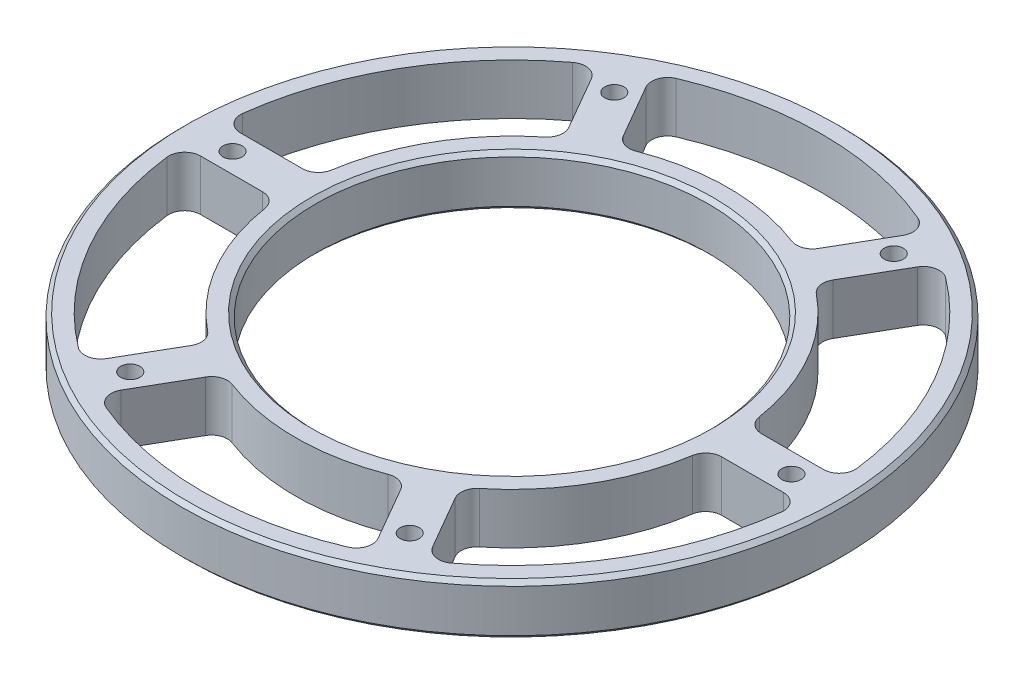
SolidWorks part; units mm, degrees
material "6061-T6 (SS)"
ref_plane "Front Plane" through (0, 0, 0) normal (0, 0, 1) x (1, 0, 0)
ref_plane "Top Plane" through (0, 0, 0) normal (0, 1, 0) x (1, 0, 0)
ref_plane "Right Plane" through (0, 0, 0) normal (1, 0, 0) x (0, 0, -1)
sketch "Sketch2" plane through (0, 0, 0) normal (1, 0, 0) x (0, 0, -1)
  line L0 (-49.2125, 0) -> (-82.55, 0)
  line L1 (-82.55, 0) -> (-82.55, 12.7)
  line L2 (-82.55, 12.7) -> (-49.2125, 12.7)
  line L3 (-49.2125, 12.7) -> (-49.2125, 0)
  dimension "D1" = 82.55
  dimension "D2" = 12.7
  dimension "D4" = 49.2125
ref_axis "Axis1" through (0, -0.635, 0) along (0, 1, 0)
revolve "Revolve1" add sketch "Sketch2" angle 360 about axis through (0, -0.635, 0) along (0, 1, 0)
hole_wizard "#12 (0.189) Diameter Hole1" positions "Sketch6" profile "Sketch7" hole size "#12" standard "ANSI Inch" end condition through all
sketch "Sketch6" plane through (0, 12.7, 0) normal (0, 1, 0) x (1, 0, 0)
  line L0 (0, 0) -> (-69.8201, 120.932) construction
  line L2 (0, 0) -> (0, 109.0908) construction
  point P0 (-35, 60.6218)
  dimension "D1" = 30
  dimension "D2" = 70
sketch "Sketch7" plane through (-35, 12.7, -60.6218) normal (1, 0, 0) x (0, 0, 1)
  line L0 (0, 0) -> (0, 12.7)
  line L1 (0, 12.7) -> (2.4003, 12.7)
  line L2 (2.4003, 12.7) -> (2.4003, 0)
  line L5 (2.4003, 0) -> (0, 0)
  line L11 (0, -6.35) -> (0, 107.95) construction
  dimension "Thru Hole Dia." = 4.8006
  dimension "Thru Hole Depth" = 12.7
pattern_circular "CirPattern3" count 6 over 360 about axis through (0, -0.635, 0) along (0, 1, 0) of "#12 (0.189) Diameter Hole1"
sketch "Sketch8" plane through (0, 12.7, 0) normal (0, 1, 0) x (1, 0, 0)
  line L4 (0, 0) -> (0, 93.9995) construction
  line L5 (-22.6606, 49.2493) -> (-34.3642, 69.5205)
  line L6 (22.6606, 49.2493) -> (34.3642, 69.5205)
  line L7 (0, 0) -> (-35, 60.6218) construction
  arc A0 (-22.6606, 49.2493) -> (22.6606, 49.2493) centre (0, 0) cw
  arc A1 (-34.3642, 69.5205) -> (34.3642, 69.5205) centre (0, 0) cw
  circle A2 centre (0, 0) radius 82.55 construction
  circle A4 centre (0, 0) radius 49.2125 construction
  dimension "D1" = 5
  dimension "D2" = 5
  dimension "D3" = 5
extrude "Cut-Extrude1" cut sketch "Sketch8" against normal through all
fillet "Fillet1" radius 4 4 edges at (-22.6606, 6.35, -49.2493) (22.6606, 6.35, -49.2493) (34.3642, 6.35, -69.5205) (-34.3642, 6.35, -69.5205)
pattern_circular "CirPattern4" count 6 over 360 about axis through (0, -0.635, 0) along (0, 1, 0) of "Cut-Extrude1", "Fillet1"
chamfer "Chamfer1" distance 1 angle 45 2 edges at (0, 12.7, -49.2125) (0, 0, -49.2125)
chamfer "Chamfer2" distance 1 angle 45 2 edges at (0, 12.7, -82.55) (0, 0, -82.55)
equation "\"TubeDiameter\" = 6.500in"
equation "\"D1@Sketch2\"=\"TubeDiameter\"/2"
